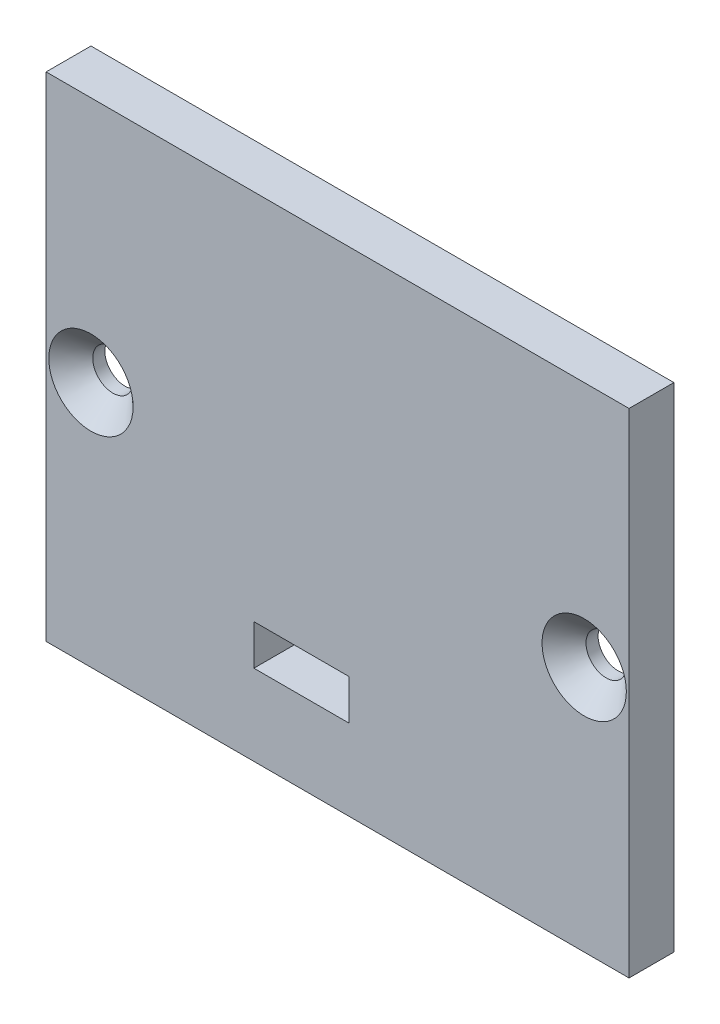
SolidWorks part; units mm, degrees
ref_plane "Plan de face" through (0, 0, 0) normal (0, 0, 1) x (1, 0, 0)
ref_plane "Plan de dessus" through (0, 0, 0) normal (0, 1, 0) x (1, 0, 0)
ref_plane "Plan de droite" through (0, 0, 0) normal (1, 0, 0) x (0, 0, -1)
sketch "Esquisse1" plane through (0, 0, 0) normal (0, 0, 1) x (1, 0, 0)
  line L1 (0, 0) -> (65, 0)
  line L2 (0, 0) -> (0, 55)
  line L3 (0, 55) -> (65, 55)
  line L4 (65, 0) -> (65, 55)
  dimension "D1" = 65
  dimension "D2" = 55
extrude "Boss.-Extru.1" add sketch "Esquisse1" along normal blind 5
sketch "Esquisse2" plane through (0, 0, 5) normal (0, 0, 1) x (1, 0, 0)
  line L0 (0, 55) -> (5, 55) construction
  line L1 (65, 55) -> (0, 55) construction
  line L2 (5, 55) -> (5, 0) construction
  line L3 (0, 0) -> (65, 0) construction
  line L4 (0, 55) -> (0, 0) construction
  line L5 (0, 0) -> (0, 27.5) construction
  line L6 (0, 27.5) -> (65, 27.5) construction
  line L7 (65, 0) -> (65, 55) construction
  line L8 (0, 55) -> (65, 55) construction
  line L9 (65, 55) -> (32.5, 55) construction
  line L10 (32.5, 55) -> (32.5, 0) construction
  circle A0 centre (5, 27.5) radius 2
  circle A1 centre (60, 27.5) radius 2
  dimension "D2" = 4
  dimension "D1" = 5
extrude "Enlèv. mat.-Extru.1" cut sketch "Esquisse2" against normal through all
hole_wizard "Fraisage pour vis à tête fraisée M41" positions "Esquisse5" profile "Esquisse4" countersink size "M4" standard "Ansi Metric" end condition through all
sketch "Esquisse5" plane through (0, 0, 5) normal (0, 0, 1) x (1, 0, 0)
  point P0 (5, 27.5)
  point P3 (60, 27.5)
sketch "Esquisse4" plane through (5, 27.5, 5) normal (1, 0, 0) x (0, -1, 0)
  line L0 (0, 0) -> (0, 5)
  line L1 (0, 5) -> (2.25, 5)
  line L2 (2.25, 5) -> (2.25, 2.45)
  line L3 (2.25, 2.45) -> (4.7, 0)
  line L5 (4.7, 0) -> (0, 0)
  line L6 (-2.25, 2.45) -> (-4.7, 0) construction
  line L11 (0, -6.35) -> (0, 107.95) construction
  dimension "Diamètre du perçage jusqu'au prochain" = 4.5
  dimension "Profondeur du perçage jusqu'au prochain" = 5
  dimension "Diamètre du fraisage entrant" = 9.4
  dimension "Angle du fraisage entrant" = 90
sketch "Esquisse6" plane through (0, 0, 5) normal (0, 0, 1) x (1, 0, 0)
  line L0 (0, 0) -> (0, 9) construction
  line L1 (0, 55) -> (0, 0) construction
  line L2 (0, 9) -> (65, 9) construction
  line L3 (65, 0) -> (65, 55) construction
  line L4 (65, 9) -> (65, 0) construction
  line L5 (0, 9) -> (32.5, 9) construction
  line L6 (0, 9) -> (23.1684, 9) construction
  line L7 (65, 9) -> (33.7684, 9) construction
  line L8 (23.1684, 9) -> (23.1684, 13.5)
  line L9 (23.1684, 13.5) -> (33.7684, 13.5)
  line L10 (33.7684, 13.5) -> (33.7684, 9)
  line L11 (33.7684, 9) -> (23.1684, 9)
  line L12 (0, 9) -> (33.7684, 9) construction
  line L13 (65, 9) -> (32.5, 9) construction
  dimension "D1" = 9
  dimension "D2" = 9
  dimension "D3" = 32.5
  dimension "D5" = 4.5
extrude "Enlèv. mat.-Extru.2" cut sketch "Esquisse6" against normal through all
sketch "Esquisse7" plane through (0, 0, 0) normal (0, 0, -1) x (-1, 0, 0)
  circle A0 centre (-60, 27.5) radius 4.6
  circle A1 centre (-5, 27.5) radius 4.6
  dimension "D1" = 9.2
  dimension "D2" = 9.2
extrude "Enlèv. mat.-Extru.3" cut sketch "Esquisse7" against normal blind 1.2
